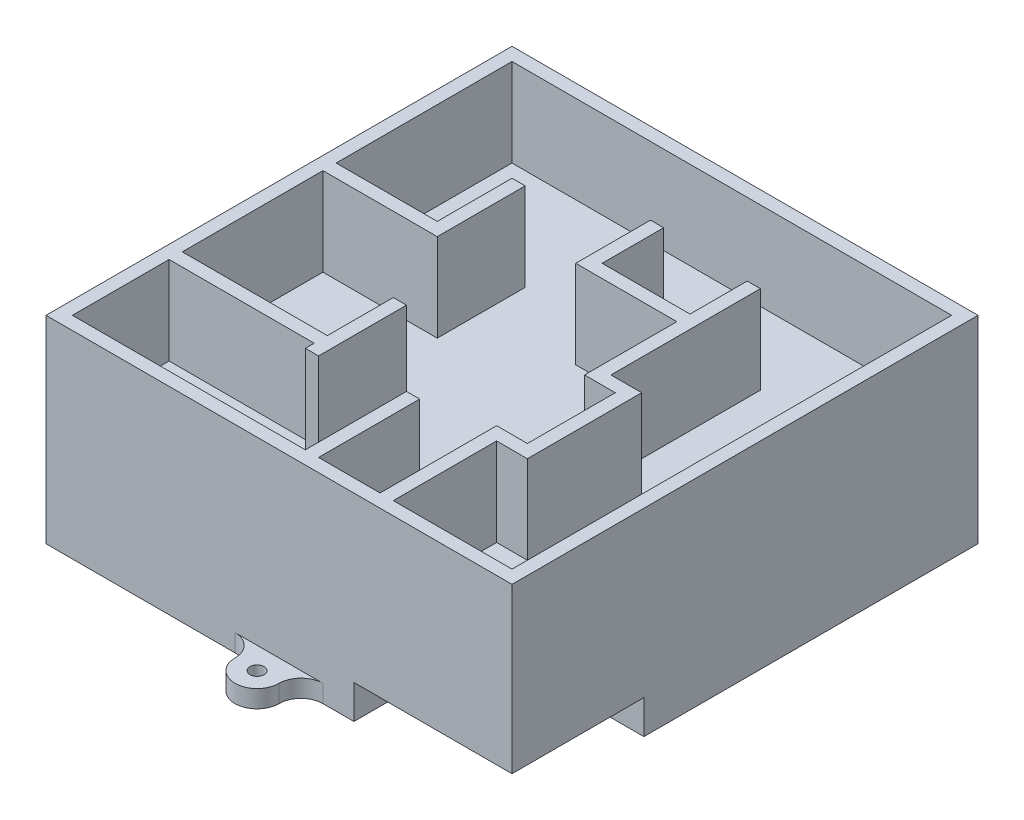
SolidWorks part; units mm, degrees
ref_plane "Front Plane" through (0, 0, 0) normal (0, 0, 1) x (1, 0, 0)
ref_plane "Top Plane" through (0, 0, 0) normal (0, 1, 0) x (1, 0, 0)
ref_plane "Right Plane" through (0, 0, 0) normal (1, 0, 0) x (0, 0, -1)
sketch "Sketch2" plane through (0, 0, 0) normal (0, 1, 0) x (1, 0, 0)
  line L1 (0, 0) -> (106, 0)
  line L2 (0, 0) -> (0, 106)
  line L3 (0, 106) -> (106, 106)
  line L4 (106, 0) -> (106, 106)
  circle A0 centre (18, 15) radius 4
  circle A1 centre (92, 13.5) radius 6
  dimension "D3" = 8
  dimension "D4" = 12
  dimension "D5" = 15
  dimension "D6" = 18
  dimension "D7" = 13.5
  dimension "D8" = 14
  dimension "D1" = 106
  dimension "D2" = 106
extrude "Boss-Extrude1" add sketch "Sketch2" along normal blind 25
sketch "Sketch3" plane through (0, 25, 0) normal (0, 1, 0) x (1, 0, 0)
  line L0 (3, 103) -> (3, 3)
  line L1 (0, 106) -> (106, 106)
  line L2 (0, 106) -> (0, 0)
  line L3 (0, 0) -> (106, 0)
  line L4 (106, 106) -> (106, 0)
  line L5 (3, 3) -> (103, 3)
  line L6 (103, 103) -> (103, 3)
  line L7 (3, 103) -> (103, 103)
  dimension "D1" = 3
extrude "Boss-Extrude2" add sketch "Sketch3" along normal blind 20
sketch "Sketch5" plane through (0, 25, 0) normal (0, 1, 0) x (1, 0, 0)
  line L2 (3, 28) -> (3, 25)
  line L5 (3, 103) -> (3, 3) construction
  line L6 (83, 52.5) -> (83, 26.5)
  line L9 (36, 43) -> (39, 43)
  line L10 (39, 23) -> (39, 43)
  line L12 (3, 63) -> (3, 60)
  line L19 (26, 63) -> (26, 80)
  line L20 (3, 3) -> (103, 3) construction
  line L21 (56, 3) -> (59, 3)
  line L22 (56, 3) -> (56, 26)
  line L23 (56, 26) -> (59, 26)
  line L24 (59, 3) -> (59, 26)
  line L25 (3, 28) -> (36, 28)
  line L26 (3, 3) -> (103, 3) construction
  line L27 (73, 3) -> (76, 3)
  line L30 (76, 3) -> (76, 26.5)
  line L38 (80, 29.5) -> (80, 49.5)
  line L41 (80, 49.5) -> (73, 49.5)
  line L42 (73, 52.5) -> (73, 49.5)
  line L44 (76, 26.5) -> (83, 26.5)
  line L45 (73, 52.5) -> (83, 52.5)
  line L47 (3, 63) -> (26, 63)
  line L50 (80, 29.5) -> (73, 29.5)
  line L51 (73, 29.5) -> (73, 3)
  line L52 (29, 60) -> (3, 60)
  line L53 (29, 60) -> (29, 80)
  line L54 (29, 80) -> (26, 80)
  line L55 (36, 43) -> (36, 28)
  line L56 (3, 25) -> (36, 25)
  line L57 (36, 25) -> (36, 23)
  line L58 (36, 23) -> (39, 23)
  dimension "D3" = 0
extrude "Boss-Extrude3" add sketch "Sketch5" along normal blind 20 contours L9 L10 L58 L57 L56 L2 L25 L55 | L54 L19 L47 L12 L52 L53 | L22 L21 L24 L23 | L51 L27 L30 L44 L6 L45 L42 L41 L38 L50
sketch "Sketch7" plane through (0, 25, 0) normal (0, 1, 0) x (1, 0, 0)
  line L1 (73, 52.5) -> (76, 52.5)
  line L2 (73, 52.5) -> (73, 86.5)
  line L3 (73, 86.5) -> (76, 86.5)
  line L4 (76, 52.5) -> (76, 86.5)
  line L5 (73, 73.4965) -> (53, 73.4965)
  line L6 (73, 73.4965) -> (73, 70.4965)
  line L7 (73, 70.4965) -> (53, 70.4965)
  line L8 (53, 73.4965) -> (53, 70.4965)
  line L9 (53, 70.4965) -> (50, 70.4965)
  line L10 (53, 70.4965) -> (53, 87.4965)
  line L11 (53, 87.4965) -> (50, 87.4965)
  line L12 (50, 70.4965) -> (50, 87.4965)
  line M14 (73, 52.5) -> (83, 52.5)
  dimension "D1" = 3
  dimension "D2" = 3
  dimension "D3" = 3
  dimension "D4" = 34
  dimension "D5" = 20
  dimension "D6" = 17
extrude "Boss-Extrude4" add sketch "Sketch7" along normal blind 20 contours L12 L9 L8 L10 L11 | L5 L8 L7 L2 | L4 L3 L2 M14 region at (74.5, 25, -69.5) region at (63, 25, -71.9965) region at (51.5, 25, -78.9965)
sketch "Sketch9" plane through (0, 25, 0) normal (0, 1, 0) x (1, 0, 0)
  circle A0 centre (92, 13.5) radius 9.9058
extrude "Cut-Extrude1" cut sketch "Sketch9" against normal blind 10
fillet "Fillet1" [suppressed] radius 5
sketch "Sketch10" plane through (0, 0, 0) normal (0, 0, 1) x (1, 0, 0)
  line L0 (0, 0) -> (106, 0) construction
  line L1 (48, 4) -> (58, 4)
  line L2 (48, 4) -> (48, 0)
  line L3 (48, 0) -> (58, 0)
  line L4 (58, 4) -> (58, 0)
  line L5 (0, 45) -> (106, 45) construction
  point P6 (53, 4)
  point P9 (53, 45)
  dimension "D1" = 10
  dimension "D2" = 4
  dimension "D3" = 0
  dimension "D4" = 0
extrude "Boss-Extrude5" add sketch "Sketch10" along normal blind 10
sketch "Sketch11" plane through (0, 0, -106) normal (0, 0, -1) x (-1, 0, 0)
  line L0 (-106, 45) -> (0, 45) construction
  line L1 (-58, 4) -> (-48, 4)
  line L2 (-58, 4) -> (-58, 0)
  line L3 (-58, 0) -> (-48, 0)
  line L4 (-48, 4) -> (-48, 0)
  line L5 (-106, 0) -> (0, 0) construction
  point P4 (-53, 4)
  point P7 (-53, 45)
  dimension "D1" = 10
  dimension "D2" = 4
  dimension "D3" = 0
  dimension "D4" = 0
extrude "Boss-Extrude6" add sketch "Sketch11" along normal blind 10
fillet "Fillet2" 2 edges at (48, 2, -116) (58, 2, -116) type full round first side face at (48, 2, -111) second side face at (58, 2, -111) middle face at (53, 2, -116)
fillet "Fillet3" radius 5 2 edges at (48, 2, -106) (58, 2, -106)
fillet "Fillet4" radius 5 2 edges at (48, 2, 0) (58, 2, 0)
fillet "Fillet5" 2 edges at (48, 2, 10) (58, 2, 10) type full round first side face at (48, 2, 7.5) second side face at (58, 2, 7.5) middle face at (53, 2, 10)
sketch "Sketch13" plane through (0, 4, 0) normal (0, 1, 0) x (1, 0, 0)
  circle A0 centre (53, -5) radius 1.6
  circle A1 centre (53, 111) radius 1.6
  dimension "D1" = 3.2
  dimension "D2" = 3.2
extrude "Cut-Extrude2" cut sketch "Sketch13" against normal through all
sketch "Sketch14" plane through (0, 0, 0) normal (0, 0, 1) x (1, 0, 0)
  line L1 (106, 0) -> (70.0395, 0)
  line L2 (106, 0) -> (106, 7.6935)
  line L3 (106, 7.6935) -> (70.0395, 7.6935)
  line L4 (70.0395, 0) -> (70.0395, 7.6935)
extrude "Cut-Extrude3" cut sketch "Sketch14" against normal blind 30
